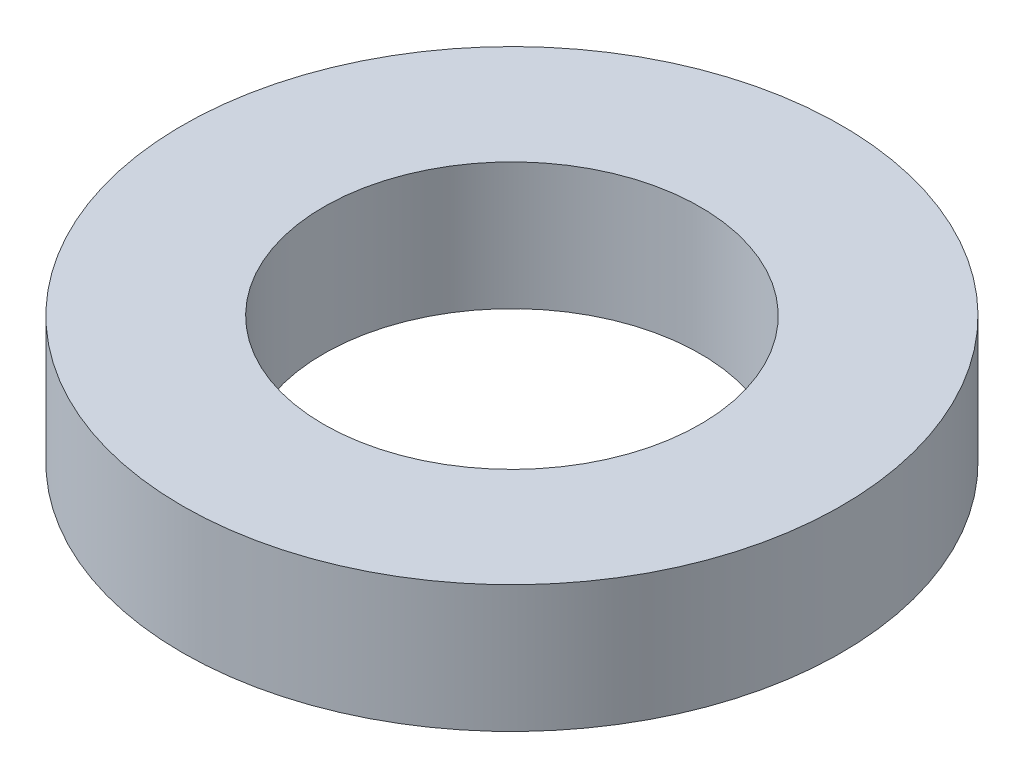
SolidWorks part; units mm, degrees
ref_plane "Front Plane" through (0, 0, 0) normal (0, 0, 1) x (1, 0, 0)
ref_plane "Top Plane" through (0, 0, 0) normal (0, 1, 0) x (1, 0, 0)
ref_plane "Right Plane" through (0, 0, 0) normal (1, 0, 0) x (0, 0, -1)
sketch "Sketch1" plane through (0, 0, 0) normal (0, 1, 0) x (1, 0, 0)
  circle A0 centre (0, 0) radius 70
  dimension "FLANGE_OD" = 140
extrude "Boss-Extrude1" add sketch "Sketch1" along normal blind 27
sketch "Sketch2" plane through (0, 0, 0) normal (0, 1, 0) x (1, 0, 0)
  circle A0 centre (0, 0) radius 40
  dimension "BORE_D" = 80
extrude "Cut-Extrude1" cut sketch "Sketch2" along normal through all
sketch "Sketch3" plane through (0, 27, 0) normal (0, 1, 0) x (1, 0, 0)
  circle A0 centre (0, 0) radius 28.3851 construction
  circle A1 centre (-28.3851, 0) radius 4.5515
  dimension "BOLT_D" = 9.103
  dimension "BOLT_PCD" = 56.7702
extrude "Cut-Extrude2" cut sketch "Sketch3" against normal blind 19.9984 rebuild error yes
pattern_circular "CirPattern1" count 8 over 360 rebuild error yes
